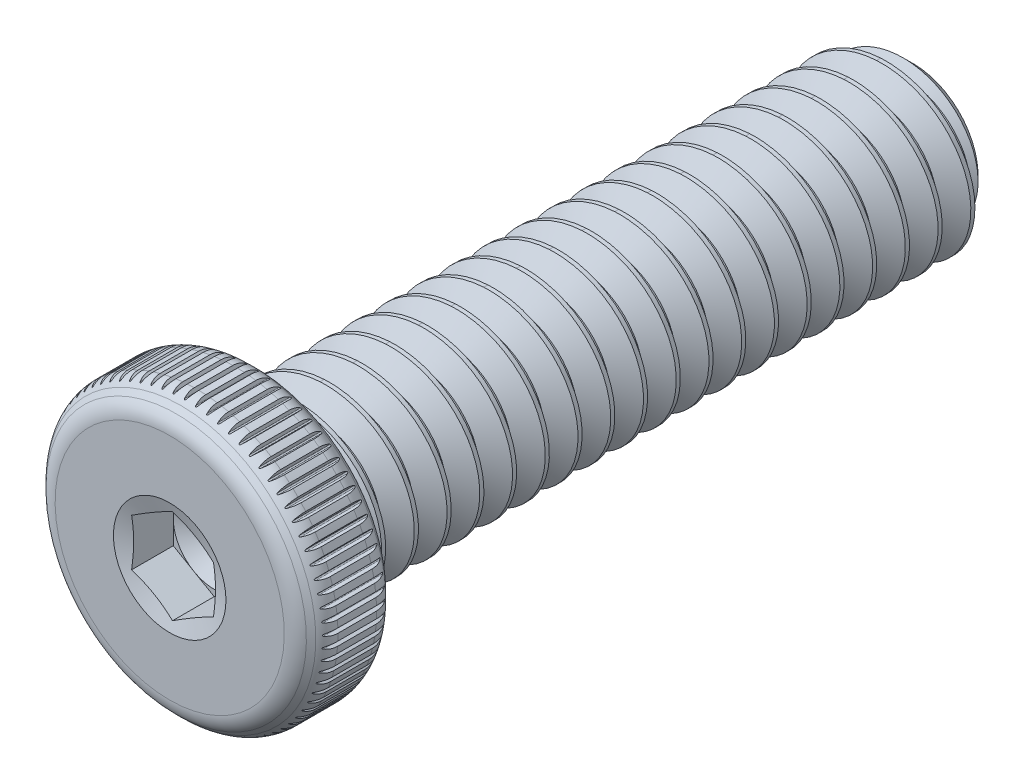
SolidWorks part; units mm, degrees
ref_plane "Front Plane" through (0, 0, 0) normal (0, 0, 1) x (1, 0, 0)
ref_plane "Top Plane" through (0, 0, 0) normal (0, 1, 0) x (1, 0, 0)
ref_plane "Right Plane" through (0, 0, 0) normal (1, 0, 0) x (0, 0, -1)
sketch "Sketch1" plane through (0, 0, 0) normal (1, 0, 0) x (0, 0, -1)
  line L0 (-9.017, 0) -> (9.017, 0) construction
  line L1 (-9.017, 0) -> (-9.017, 3.429)
  line L2 (-9.017, 3.429) -> (-6.858, 3.429)
  line L3 (-6.858, 3.429) -> (-6.858, 2.0828)
  line L4 (-6.858, 2.0828) -> (8.5014, 2.0828)
  line L5 (8.9674, 2.1687) -> (9.3643, 1.4813) construction
  line L6 (9.3643, 1.4813) -> (9.7611, 2.1687) construction
  line L7 (9.7611, 2.1687) -> (8.9674, 2.1687) construction
  line L8 (8.5014, 2.0828) -> (9.017, 1.5672)
  line L9 (9.017, 1.5672) -> (9.017, 0)
  line L10 (9.017, 2.0828) -> (9.7115, 2.0828) construction
  line L11 (9.3643, 2.1687) -> (9.3643, 2.0828) construction
  line L12 (9.3643, 2.0828) -> (9.3643, 1.5672) construction
  line L13 (9.3643, 1.5672) -> (9.3643, 1.4813) construction
  line L14 (9.3147, 1.5672) -> (9.4139, 1.5672)
  line L15 (8.9922, 2.1258) -> (9.7363, 2.1258)
  line L16 (9.4139, 1.5672) -> (9.7363, 2.1258)
  line L17 (9.3147, 1.5672) -> (8.9922, 2.1258)
  line L18 (-9.017, 0.9922) -> (-7.9375, 0.9922)
  line L19 (-7.9375, 0.9922) -> (-7.9375, 0)
  line L20 (6.2389, 2.0828) -> (6.2389, -2.0828) construction
  point P20 (9.3643, 2.1258)
  point P22 (6.2389, -2.0828)
  point P28 (6.2389, 0)
  point P29 (8.5014, -2.0828)
  point P30 (-7.3978, 3.429)
  dimension "Head Diameter" = 6.858
  dimension "Length" = 15.875
  dimension "Head Height" = 2.159
  dimension "Screw Size Decimal Equivalent" = 4.1656
  dimension "D1" = 45
  dimension "Thread Pitch" = 0.7937
  dimension "D3" = 0.0992
  dimension "Drive Size" = 1.9844
  dimension "D4" = 2.7781
  dimension "D5" = 1.0795
  dimension "D2" = 1.6193
sketch "Sketch3" plane through (0, 0, 0) normal (1, 0, 0) x (0, 0, -1)
  line L0 (-9.017, 2.7784) -> (-9.017, 0.9922)
  line L1 (-9.017, 0.9922) -> (-7.9375, 0.9922)
  line L2 (-7.9375, 0.9922) -> (-7.9375, 0)
  line L3 (-7.9375, 0) -> (9.017, 0)
  line L4 (9.017, 0) -> (9.017, 1.5672)
  line L5 (9.017, 1.5672) -> (8.5014, 2.0828)
  line L6 (8.5014, 2.0828) -> (-6.858, 2.0828)
  line L7 (-6.858, 2.0828) -> (-6.858, 2.9679)
  line L8 (-7.4301, 3.429) -> (-8.3664, 3.429)
  line L9 (-8.8601, 3.1573) -> (-8.7453, 3.2721)
  line L10 (-7.0512, 3.2721) -> (-6.9365, 3.1573)
  line L11 (-9.017, 3.429) -> (-6.858, 3.429) construction
  arc A0 (-8.7453, 3.2721) -> (-8.3664, 3.429) centre (-8.3664, 2.8932) cw
  arc A1 (-8.8601, 3.1573) -> (-9.017, 2.7784) centre (-8.4812, 2.7784) ccw
  arc A2 (-6.9365, 3.1573) -> (-6.858, 2.9679) centre (-7.1259, 2.9679) cw
  arc A3 (-7.0512, 3.2721) -> (-7.4301, 3.429) centre (-7.4301, 2.8932) ccw
  point P25 (-9.017, 3.0004)
  dimension "D3" = 0.5358
  dimension "D4" = 0.2679
  dimension "D1" = 45
  dimension "D2" = 0.4286
revolve "Revolve1" add sketch "Sketch3" angle 360 about L0
sketch "Sketch4" plane through (0, 0, 9.017) normal (0, 0, 1) x (1, 0, 0)
  line L1 (0, 1.1457) -> (-0.9922, 0.5728)
  line L2 (-0.9922, 0.5728) -> (-0.9922, -0.5728)
  line L3 (-0.9922, -0.5728) -> (0, -1.1457)
  line L4 (0, -1.1457) -> (0.9922, -0.5728)
  line L5 (0.9922, -0.5728) -> (0.9922, 0.5728)
  line L6 (0.9922, 0.5728) -> (0, 1.1457)
  circle A0 centre (0, 0) radius 0.9922 construction
extrude "Cut-Extrude1" cut sketch "Sketch4" against normal up to vertex (1.0795 mm away) up to point (0, 0.9922, 7.9375)
sketch "Sketch5" plane through (0, 0, 9.017) normal (0, 0, 1) x (1, 0, 0)
  circle A0 centre (0, 0) radius 1.3643
  circle A1 centre (0, 0) radius 3.429 construction
  dimension "D1" = 2.7285
extrude "Cut-Extrude2" cut sketch "Sketch5" against normal up to next (1.0795 mm away) draft 72.5
sketch "Sketch10" plane through (0, 0, 7.9375) normal (0, 0, 1) x (1, 0, 0)
  line L0 (0.9922, 0.5728) -> (0.9922, -0.5728) construction
  circle A0 centre (0, 0) radius 0.9922
extrude "Cut-Extrude3" cut sketch "Sketch10" against normal through all draft 60
split "Split1" bodies to split 112 resulting bodies 107 108 split by face at (0, -2.9679, 6.858)
sketch "Sketch6" plane through (0, 0, -9.017) normal (0, 0, -1) x (-1, 0, 0)
  circle A0 centre (0, 0) radius 2.0828 construction
  circle A1 centre (0, 0) radius 2.0828
curve "Helix/Spiral1" pitch 0.7937 height 16.2719 radius 2.0828 centre (0, 0, -9.017) axis (0, 0, 1) start towards (0, 1, 0)
sketch "Sketch7" plane through (0, 0, 0) normal (1, 0, 0) x (0, 0, -1)
  line L0 (9.3147, 1.5672) -> (9.4139, 1.5672) construction
  line L1 (9.3147, 1.5672) -> (8.9922, 2.1258) construction
  line L2 (8.9922, 2.1258) -> (9.7363, 2.1258) construction
  line L3 (9.4139, 1.5672) -> (9.7363, 2.1258) construction
  line L4 (9.3147, 1.5672) -> (9.4139, 1.5672)
  line L5 (9.3147, 1.5672) -> (8.9922, 2.1258)
  line L6 (8.9922, 2.1258) -> (9.7363, 2.1258)
  line L7 (9.4139, 1.5672) -> (9.7363, 2.1258)
sweep "Cut-Sweep1" cut profiles "Sketch7" path "Helix/Spiral1" align with end faces yes
sketch "Sketch11" plane through (0, 0, 0) normal (1, 0, 0) x (0, 0, -1)
  line L0 (-6.858, 2.2812) -> (-6.6596, 2.0828)
  line L1 (-6.858, 3.429) -> (-6.858, 2.0828) construction
  line L2 (-6.858, 2.0828) -> (8.5014, 2.0828) construction
  line L3 (-6.6596, 2.0828) -> (-6.4611, 2.0828)
  line L4 (-6.4611, 2.0828) -> (-4.3783, 0)
  line L5 (-9.017, 0) -> (9.017, 0) construction
  line L6 (-4.3783, 0) -> (-6.858, 0)
  line L7 (-6.858, 0) -> (-6.858, 2.2812) construction
  line L8 (-6.858, 2.2812) -> (-7.3647, 2.2812)
  line L9 (-7.3647, 2.2812) -> (-7.3647, 0)
  line L10 (-7.3647, 0) -> (-6.858, 0)
  dimension "D1" = 45
  dimension "D2" = 0.1984
  dimension "D3" = 45
  dimension "D4" = 0.3969
revolve "Revolve2" add sketch "Sketch11" angle 360 about L6
sketch "Sketch12" plane through (0, 0, 9.017) normal (0, 0, 1) x (1, 0, 0)
  line L0 (0, 0) -> (0, 3.429) construction
  line L1 (0, 0) -> (0.1715, 3.6621) construction
  line L2 (0.1715, 3.6621) -> (-0.1715, 3.6621)
  line L3 (-0.1715, 3.6621) -> (0, 0) construction
  line L4 (-0.1715, 3.6621) -> (-0.0192, 3.3548)
  line L5 (0.0192, 3.3548) -> (0.1715, 3.6621)
  line L7 (0, 2.7784) -> (0, 3.1573) construction
  circle A0 centre (0, 0) radius 3.429 construction
  arc A2 (-0.0192, 3.3548) -> (0.0192, 3.3548) centre (0, 3.3644) ccw
  point P11 (0, 3.3161)
  point P13 (0, 3.3429)
  point P17 (0, 2.9679)
  dimension "D3" = 0.0214
  dimension "D1" = 0.3429
  dimension "D2" = 5.361
  dimension "D5" = 0.375
extrude "Cut-Extrude4" cut sketch "Sketch12" against normal through all
pattern_circular "CirPattern1" count 77 over 360 about axis through (0, 0, 8.7453) along (0, 0, 1) of "Cut-Extrude4"
equation "\"D3@Sketch1\" = \"Thread Pitch@Sketch1\" / 8"
equation "\"D4@Sketch1\" = \"Thread Pitch@Sketch1\" * 3.5"
equation "\"D3@Helix/Spiral1\"=\"Length@Sketch1\" +( \"Thread Pitch@Sketch1\"*0.5)"
equation "\"D4@Helix/Spiral1\" = \"Thread Pitch@Sketch1\""
equation "\"D5@Sketch1\"=\"Head Height@Sketch1\"*0.5"
equation "\"D2@Sketch3\"=\"Head Diameter@Sketch1\"*0.0625"
equation "\"D2@Sketch11\"=\"Thread Pitch@Sketch1\" / 4"
equation "\"D1@Sketch12\"=\"Head Diameter@Sketch1\"*0.05"
equation "\"D1@CirPattern1\"=int(360/\"D2@Sketch12\")+10"
equation "\"D3@Sketch12\"=\"D1@Sketch12\"*0.0625"
equation "\"D3@Sketch3\"=\"D2@Sketch3\"*1.25"
equation "\"D5@Sketch12\"=\"D2@Sketch3\"*0.875"
equation "\"D2@Sketch1\"=\"Head Height@Sketch1\"*0.75"
equation "\"D4@Sketch11\"=\"Thread Pitch@Sketch1\"*0.5"
equation "\"D4@Sketch3\"=\"D3@Sketch3\"*0.5"
equation "\"D1@Sketch5\"=\"Drive Size@Sketch1\"*1.375"
